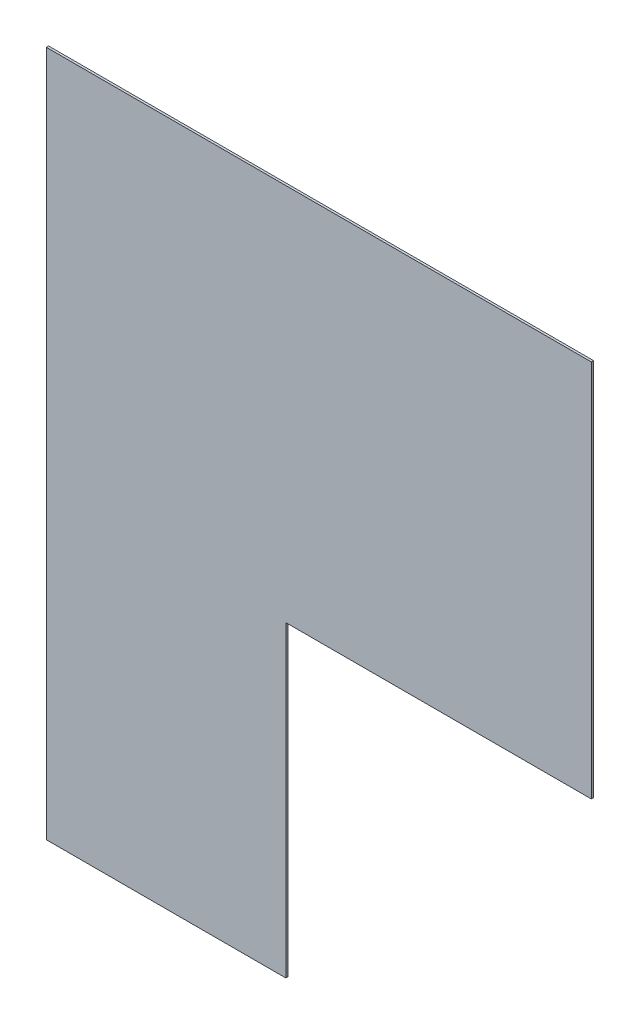
SolidWorks part; units mm, degrees
material "Hardox"
ref_plane "Ön Düzlem" through (0, 0, 0) normal (0, 0, 1) x (1, 0, 0)
ref_plane "Üst Düzlem" through (0, 0, 0) normal (0, 1, 0) x (1, 0, 0)
ref_plane "Sağ Düzlem" through (0, 0, 0) normal (1, 0, 0) x (0, 0, -1)
sketch "Çizim1" plane through (0, 0, 0) normal (0, 0, 1) x (1, 0, 0)
  line L0 (0, 0) -> (1195, 0)
  line L1 (1195, 0) -> (1195, -895)
  line L2 (1195, -895) -> (1800, -895)
  line L3 (1800, -895) -> (1800, -1505)
  line L4 (1800, -1505) -> (0, -1505)
  line L5 (0, -1505) -> (0, 0)
  dimension "D1" = 1195
  dimension "D2" = 895
  dimension "D3" = 605
  dimension "D4" = 610
  dimension "D5" = 1800
  dimension "D6" = 1505
base flange "Taban-Flanş1" sketch "Çizim1" thickness 5 reverse thickness direction no parameters "D1"=12
sketch "Çizim2" plane through (0, 0, 0) normal (0, 0, 1) x (1, 0, 0)
  line L0 (525, -1505) -> (525, -830)
  line L1 (0, -1505) -> (1800, -1505) construction
  line L2 (525, -830) -> (1195, -830)
  line L3 (1195, -895) -> (1195, 0) construction
  line L4 (1800, -1505) -> (1800, -895) construction
  line L5 (1800, -895) -> (1195, -895) construction
  line L6 (1195, -830) -> (1965.5283, -849.7447)
  line L7 (1965.5283, -849.7447) -> (1943.2613, -1718.704)
  line L8 (1943.2613, -1718.704) -> (525, -1505)
  dimension "D1" = 1275
  dimension "D2" = 675
  dimension "D3" = 670
  dimension "D4" = 605
  dimension "D5" = 610
extrude "Kes-Ekstrüzyon1" cut sketch "Çizim2" against normal through all both and the other way through all
sketch "Büküm-Çizgileri1" [suppressed] plane through (0, 0, 0) normal (0, 1, 0) x (1, 0, 0)
sketch "Sınırlandırma-Kutusu1" [suppressed] plane through (0, 0, 0) normal (0, 1, 0) x (1, 0, 0)
sheet metal parameters "Sac-Levha1" thickness 5 parameters "D1"=12
flat pattern "Düz-Çoğaltma1" [suppressed]
sketch "Büküm-Çizgileri2" plane through (0, 0, 0) normal (0, 1, 0) x (1, 0, 0)
sketch3d "Sınırlandırma-Kutusu2" [suppressed]
  line L0 (0, -1505, 0) -> (1800, -1505, 0) construction
  line L1 (0, 0, 0) -> (1800, 0, 0) construction
  line L2 (0, -1505, 0) -> (0, 0, 0) construction
  line L3 (1800, -1505, 0) -> (1800, 0, 0) construction
sheet metal parameters "Sac-Levha2" thickness 5 parameters "D1"=12
flat pattern "Düz-Çoğaltma1" [suppressed]
sketch "Büküm-Çizgileri2" plane through (0, 0, 0) normal (0, 1, 0) x (1, 0, 0)
sketch3d "Sınırlandırma-Kutusu2" [suppressed]
  line L0 (1195, 0, 0) -> (1195, -1505, 0) construction
  line L1 (0, 0, 0) -> (0, -1505, 0) construction
  line L2 (1195, 0, 0) -> (0, 0, 0) construction
  line L3 (1195, -1505, 0) -> (0, -1505, 0) construction
